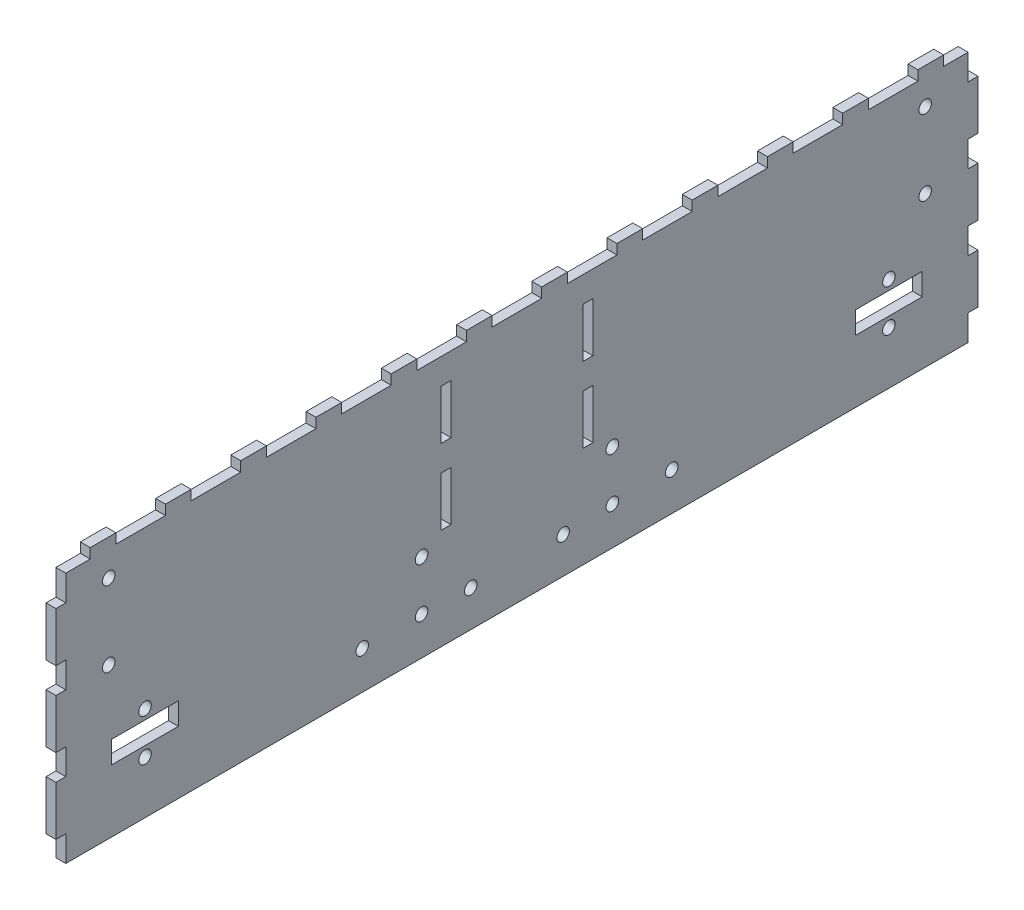
SolidWorks part; units mm, degrees
material "ENPH 253 Hardboard"
ref_plane "Front Plane" through (0, 0, 0) normal (0, 0, 1) x (1, 0, 0)
ref_plane "Top Plane" through (0, 0, 0) normal (0, 1, 0) x (1, 0, 0)
ref_plane "Right Plane" through (0, 0, 0) normal (1, 0, 0) x (0, 0, -1)
sketch "Sketch1" plane through (0, 0, 0) normal (1, 0, 0) x (0, 0, -1)
  line L1 (-139.7, 38.1) -> (139.7, 38.1)
  line L2 (-139.7, 38.1) -> (-139.7, -38.1)
  line L3 (-139.7, -38.1) -> (139.7, -38.1)
  line L4 (139.7, 38.1) -> (139.7, -38.1)
  line L5 (-139.7, 38.1) -> (139.7, -38.1) construction
  line L6 (-139.7, -38.1) -> (139.7, 38.1) construction
  point P0 (0, 0)
  dimension "D1" = 279.4
  dimension "D2" = 76.2
extrude "Boss-Extrude1" add sketch "Sketch1" against normal blind 3 contours L2 L3 L4 L1
sketch "Sketch3" plane through (-3, 0, 0) normal (-1, 0, 0) x (0, 0, 1)
  line L9 (-139.7, 38.1) -> (-136.7, 38.1)
  line L10 (-139.7, 38.1) -> (-139.7, 30.3)
  line L11 (-139.7, 30.3) -> (-136.7, 30.3)
  line L12 (-136.7, 38.1) -> (-136.7, 30.3)
  dimension "D9" = 7.8
  dimension "D10" = 3
extrude "Cut-Extrude1" cut sketch "Sketch3" against normal through all
pattern_linear "LPattern1" count 4 spacing 22.8 along (0, -1, 0) of "Cut-Extrude1"
mirror "Mirror1" about plane through (0, 0, 0) normal (0, 0, 1) of "LPattern1"
sketch "Sketch5" plane through (-3, 0, 0) normal (-1, 0, 0) x (0, 0, 1)
  line L1 (-23, 30.3) -> (-20, 30.3)
  line L2 (-23, 30.3) -> (-23, 15.3)
  line L3 (-23, 15.3) -> (-20, 15.3)
  line L4 (-20, 30.3) -> (-20, 15.3)
  line L5 (136.7, 38.1) -> (-136.7, 38.1) construction
  line L6 (0, -1.65) -> (0, 1.65) construction
  dimension "D1" = 20
  dimension "D2" = 3
  dimension "D3" = 7.8
  dimension "D4" = 15
extrude "Cut-Extrude3" cut sketch "Sketch5" against normal blind 10
sketch "Sketch9" plane through (0, 38.1, 0) normal (0, 1, 0) x (1, 0, 0)
  line L0 (0, -136.7) -> (0, 136.7) construction
  line L1 (0, 129.3) -> (-3, 129.3)
  line L2 (0, 129.3) -> (0, 121.5)
  line L3 (0, 121.5) -> (-3, 121.5)
  line L4 (-3, 129.3) -> (-3, 121.5)
  line L5 (-3, -136.7) -> (-3, 136.7) construction
  line L6 (0, 136.7) -> (-3, 136.7) construction
  point P10 (-1.5, 129.3)
  dimension "D1" = 7.4
  dimension "D2" = 7.8
extrude "Boss-Extrude2" add sketch "Sketch9" along normal blind 3
pattern_linear "LPattern4" count 12 spacing 22.8 along (0, 0, 1) of "Boss-Extrude2"
pattern_linear "LPattern5" count 2 spacing 22.8 along (0, -1, 0) of "Cut-Extrude3"
mirror "Mirror2" about plane through (0, 0, 0) normal (0, 0, 1) of "LPattern5"
hole_wizard "#6 Clearance Hole1" positions "Sketch10" profile "Sketch11" hole size "#6" standard "ANSI Inch" end condition up to next
sketch "Sketch10" plane through (0, 0, 0) normal (1, 0, 0) x (0, 0, -1)
  point P0 (-28.9, -11.55)
  point P3 (-28.9, -26.55)
  point P6 (28.9, -26.55)
  point P9 (28.9, -11.55)
  point P13 (-46.9, -26.55)
  point P16 (46.9, -26.55)
sketch "Sketch11" plane through (0, -11.55, 28.9) normal (0, 1, 0) x (0, 0, -1)
  line L0 (0, 0) -> (0, 3)
  line L1 (0, 3) -> (1.8986, 3)
  line L2 (1.8986, 3) -> (1.8986, 0)
  line L5 (1.8986, 0) -> (0, 0)
  line L11 (0, -6.35) -> (0, 107.95) construction
  dimension "Thru Hole Dia." = 3.7973
  dimension "Thru Hole Depth" = 3
sketch "Sketch12" plane through (0, 0, 0) normal (1, 0, 0) x (0, 0, -1)
  line L0 (0, 38.1) -> (0, -38.1) construction
  line L1 (-122.7, -12.55) -> (-102.7, -12.55) construction
  line L2 (-122.7, -12.55) -> (-122.7, -19.05) construction
  line L3 (-122.7, -19.05) -> (-102.7, -19.05) construction
  line L4 (-102.7, -12.55) -> (-102.7, -19.05) construction
  line L5 (-7.5, 38.1) -> (7.5, 38.1) construction
  line L6 (-136.7, -38.1) -> (136.7, -38.1) construction
  line L8 (-139.7, -15.3) -> (-139.7, -30.3) construction
  line L9 (-122.8, -12.45) -> (-122.8, -19.15)
  line L10 (-122.8, -19.15) -> (-102.6, -19.15)
  line L11 (-102.6, -12.45) -> (-102.6, -19.15)
  line L12 (-122.8, -12.45) -> (-102.6, -12.45)
  line L13 (102.7, -12.55) -> (102.7, -19.05) construction
  line L14 (122.7, -19.05) -> (102.7, -19.05) construction
  line L15 (122.7, -12.55) -> (102.7, -12.55) construction
  line L16 (122.8, -12.45) -> (102.6, -12.45)
  line L17 (102.6, -12.45) -> (102.6, -19.15)
  line L18 (122.8, -19.15) -> (102.6, -19.15)
  line L19 (122.8, -12.45) -> (122.8, -19.15)
  line L20 (122.7, -12.55) -> (122.7, -19.05) construction
  dimension "D1" = 20
  dimension "D2" = 17
  dimension "D3" = 19.05
  dimension "D4" = 6.5
  dimension "D5" = 0.1
extrude "Cut-Extrude4" cut sketch "Sketch12" against normal up to next
hole_wizard "#6 Clearance Hole2" positions "Sketch13" profile "Sketch14" hole size "#6" standard "ANSI Inch" end condition up to next
sketch "Sketch13" plane through (-3, 0, 0) normal (-1, 0, 0) x (0, 0, 1)
  line L0 (-122.8, -12.45) -> (-102.6, -12.45) construction
  line L1 (-102.6, -19.15) -> (-122.8, -19.15) construction
  line L2 (102.6, -12.45) -> (122.8, -12.45) construction
  line L3 (122.8, -19.15) -> (102.6, -19.15) construction
  point P0 (-112.7, -9.45)
  point P2 (-112.7, -22.15)
  point P4 (112.7, -22.15)
  point P6 (112.7, -9.45)
  point P14 (-112.7, -12.45)
  point P17 (112.7, -12.45)
  dimension "D1" = 3
  dimension "D2" = 3
  dimension "D3" = 3
  dimension "D4" = 3
sketch "Sketch14" plane through (-3, -9.45, -112.7) normal (0, 1, 0) x (0, 0, 1)
  line L0 (0, 0) -> (0, 3)
  line L1 (0, 3) -> (1.8986, 3)
  line L2 (1.8986, 3) -> (1.8986, 0)
  line L5 (1.8986, 0) -> (0, 0)
  line L11 (0, -6.35) -> (0, 107.95) construction
  dimension "Thru Hole Dia." = 3.7973
  dimension "Thru Hole Depth" = 3
hole_wizard "#6 Clearance Hole3" positions "Sketch18" profile "Sketch19" hole size "#6" standard "ANSI Inch" end condition through all
sketch "Sketch18" plane through (-3, 0, 0) normal (-1, 0, 0) x (0, 0, 1)
  point P0 (14, -27.1)
  point P2 (-14, -27.1)
sketch "Sketch19" plane through (-3, -27.1, 14) normal (0, 1, 0) x (0, 0, 1)
  line L0 (0, 0) -> (0, 3)
  line L1 (0, 3) -> (1.8986, 3)
  line L2 (1.8986, 3) -> (1.8986, 0)
  line L5 (1.8986, 0) -> (0, 0)
  line L11 (0, -6.35) -> (0, 107.95) construction
  dimension "Thru Hole Dia." = 3.7973
  dimension "Thru Hole Depth" = 3
hole_wizard "#6 Clearance Hole4" positions "Sketch21" profile "Sketch22" hole size "#6" standard "ANSI Inch" end condition through all
sketch "Sketch21" plane through (-3, 0, 0) normal (-1, 0, 0) x (0, 0, 1)
  line L1 (-139.7, 30.3) -> (-136.7, 30.3) construction
  line L2 (-139.7, 7.5) -> (-136.7, 7.5) construction
  line L3 (0, -1.65) -> (0, 1.65) construction
  point P0 (-123.7, 30.3)
  point P2 (-123.7, 7.5)
  point P5 (0, 0)
  point P8 (0, 0)
  point P11 (0, 0)
  point P16 (0, 0)
  point P19 (123.7, 7.5)
  point P20 (123.7, 30.3)
  dimension "D1" = 13
  dimension "D2" = 13
sketch "Sketch22" plane through (-3, 30.3, -123.7) normal (0, 1, 0) x (0, 0, 1)
  line L0 (0, 0) -> (0, 3)
  line L1 (0, 3) -> (1.8986, 3)
  line L2 (1.8986, 3) -> (1.8986, 0)
  line L5 (1.8986, 0) -> (0, 0)
  line L11 (0, -6.35) -> (0, 107.95) construction
  dimension "Thru Hole Dia." = 3.7973
  dimension "Thru Hole Depth" = 3
